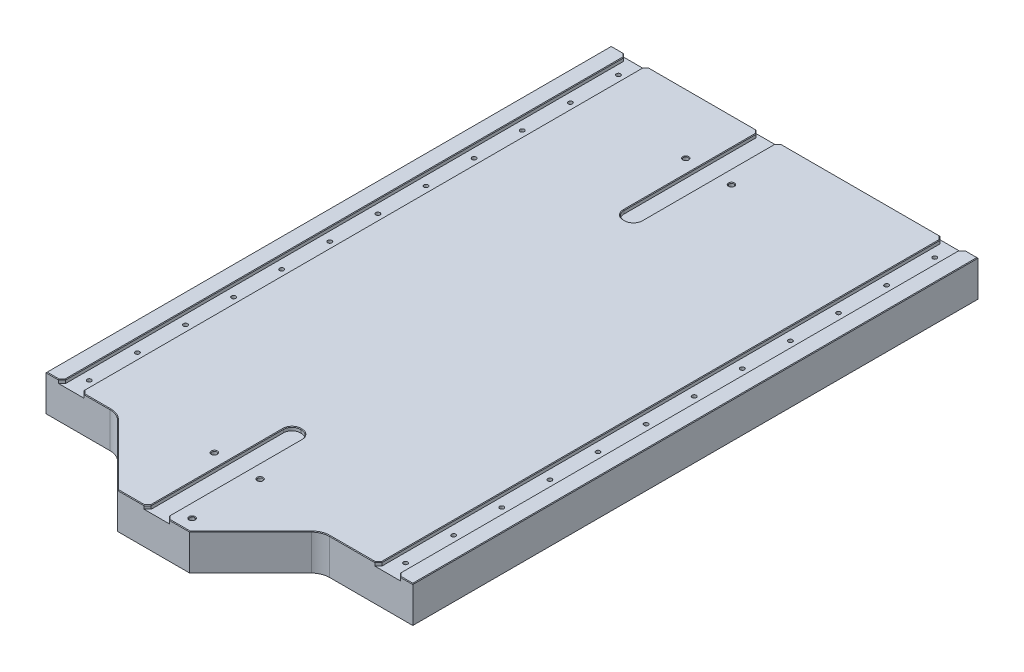
SolidWorks part; units mm, degrees
material "Acrylic (Medium-high impact)"
ref_plane "Front Plane" through (0, 0, 0) normal (0, 0, 1) x (1, 0, 0)
ref_plane "Top Plane" through (0, 0, 0) normal (0, 1, 0) x (1, 0, 0)
ref_plane "Right Plane" through (0, 0, 0) normal (1, 0, 0) x (0, 0, -1)
sketch "Sketch1" plane through (0, 0, 0) normal (0, 1, 0) x (1, 0, 0)
  line L0 (-93, -235) -> (-38, -290)
  line L1 (-152.5, -235) -> (-93, -235)
  line L2 (-152.5, -235) -> (-152.5, 235)
  line L3 (-152.5, 235) -> (152.5, 235)
  line L4 (152.5, -235) -> (152.5, 235)
  line L5 (-152.5, -235) -> (152.5, 235) construction
  line L6 (-152.5, 235) -> (152.5, -235) construction
  line L7 (-38, -290) -> (22, -290)
  line L8 (22, -290) -> (77, -235)
  line L10 (77, -235) -> (152.5, -235)
  point P0 (0, 0)
  point P10 (-38.351, -290.9295)
  point P11 (18.6696, -290.7914)
  point P12 (22.0738, -290)
  dimension "D1" = 305
  dimension "D2" = 470
  dimension "D3" = 45
  dimension "D4" = 45
  dimension "D5" = 55
  dimension "D6" = 22
  dimension "D7" = 60
extrude "Boss-Extrude1" add sketch "Sketch1" along normal blind 30
sketch "Sketch2" plane through (0, 0, 0) normal (0, 1, 0) x (1, 0, 0)
  line L0 (152.5, 235) -> (-152.5, 235) construction
  line L1 (-152.5, 235) -> (-152.5, -235) construction
  line L3 (-152.5, -235) -> (-93, -235) construction
  line L4 (0, 235) -> (0, -235) construction
  line L5 (152.5, 235) -> (-152.5, 235) construction
  line L6 (-152.5, -235) -> (-93, -235) construction
  circle A0 centre (-131.5, 220) radius 1.75
  circle A1 centre (131.5, 220) radius 1.75
  circle A4 centre (13.5, -223) radius 2
  circle A5 centre (-24.5, -223) radius 2
  circle A6 centre (-40.5, 185) radius 2
  circle A7 centre (-2.5, 185) radius 2
  circle A8 centre (131.5, -20) radius 1.75 [skipped]
  circle A9 centre (-131.5, -20) radius 1.75 [skipped]
  circle A10 centre (-131.5, 180) radius 1.75
  circle A11 centre (131.5, 180) radius 1.75
  circle A12 centre (-131.5, 140) radius 1.75
  circle A13 centre (131.5, 140) radius 1.75
  circle A14 centre (-131.5, 100) radius 1.75
  circle A15 centre (131.5, 100) radius 1.75
  circle A16 centre (-131.5, 60) radius 1.75
  circle A17 centre (131.5, 60) radius 1.75
  circle A18 centre (-131.5, 20) radius 1.75
  circle A19 centre (131.5, 20) radius 1.75
  circle A20 centre (-131.5, -20) radius 1.75
  circle A21 centre (131.5, -20) radius 1.75
  circle A22 centre (-131.5, -60) radius 1.75
  circle A23 centre (131.5, -60) radius 1.75
  circle A24 centre (-131.5, -100) radius 1.75
  circle A25 centre (131.5, -100) radius 1.75
  circle A26 centre (-131.5, -140) radius 1.75
  circle A27 centre (131.5, -140) radius 1.75
  circle A28 centre (-131.5, -180) radius 1.75
  circle A29 centre (131.5, -180) radius 1.75
  circle A30 centre (-131.5, -220) radius 1.75
  circle A31 centre (131.5, -220) radius 1.75
  circle A32 centre (13.5, -279.5) radius 2
  point P77 (4.7681, -277.9148)
  point P78 (0, 0)
  point P79 (13.5, -280.5297)
  dimension "D5" = 3.5
  dimension "D8" = 131.5
  dimension "D9" = 38
  dimension "D10" = 4
  dimension "D11" = 128
  dimension "D12" = 12
  dimension "D13" = 38
  dimension "D14" = 112
  dimension "D15" = 50
  dimension "D3" = 15
  dimension "D4" = 263
  dimension "D6" = 12
  dimension "D7" = 40
  dimension "D16" = 56.5
  dimension "D1" = 2
  dimension "D2" = 2
extrude "Cut-Extrude1" cut sketch "Sketch2" along normal through all
sketch "Sketch3" plane through (0, 30, 0) normal (0, 1, 0) x (1, 0, 0)
  line L0 (152.5, 235) -> (-152.5, 235) construction
  line L1 (-123.875, 235) -> (-139.125, 235)
  line L2 (-123.875, 235) -> (-123.875, -235)
  line L3 (-123.875, -235) -> (-139.125, -235)
  line L4 (-139.125, 235) -> (-139.125, -235)
  line L5 (-152.5, -235) -> (-93, -235) construction
  line L6 (0, 0) -> (0, 235) construction
  line L7 (-131.5, 235) -> (-131.5, 220) construction
  line L8 (123.875, -235) -> (139.125, -235)
  line L9 (123.875, 235) -> (123.875, -235)
  line L10 (123.875, 235) -> (139.125, 235)
  line L11 (131.5, 235) -> (131.5, 220) construction
  line L12 (139.125, 235) -> (139.125, -235)
  dimension "D1" = 15.25
extrude "Cut-Extrude2" cut sketch "Sketch3" against normal blind 3
sketch "Sketch4" plane through (0, 30, 0) normal (0, 1, 0) x (1, 0, 0)
  line L0 (13.5, -223) -> (-24.5, -223) construction
  line L1 (-5.5, -223) -> (-5.5, -230) construction
  line L2 (-38, -290) -> (22, -290) construction
  line L3 (2, -290) -> (-13, -290)
  line L4 (2, -290) -> (2, -170)
  line L5 (2, -170) -> (-13, -170)
  line L6 (-13, -290) -> (-13, -170)
  line L7 (2, -290) -> (-13, -170) construction
  line L8 (2, -170) -> (-13, -290) construction
  line L9 (-2.5, 185) -> (-40.5, 185) construction
  line L10 (-21.5, 185) -> (-21.5, 175) construction
  line L11 (123.875, 235) -> (-123.875, 235) construction
  line L12 (-14, 115) -> (-29, 115)
  line L13 (-14, 115) -> (-14, 235)
  line L14 (-14, 235) -> (-29, 235)
  line L15 (-29, 115) -> (-29, 235)
  line L16 (-14, 115) -> (-29, 235) construction
  line L17 (-14, 235) -> (-29, 115) construction
  dimension "D1" = 120
  dimension "D2" = 15
  dimension "D3" = 120
extrude "Cut-Extrude3" cut sketch "Sketch4" against normal blind 3
fillet "Fillet1" radius 7 4 edges at (-29, 28.5, -115) (-14, 28.5, -115) (-13, 28.5, 170) (2, 28.5, 170)
fillet "Fillet2" radius 15 2 edges at (77, 15, 235) (-93, 15, 235)
chamfer "Chamfer1" distance 3 angle 45 12 edges at (-139.125, 28.5, 235) (-123.875, 28.5, 235) (139.125, 28.5, 235) (123.875, 28.5, 235) (139.125, 28.5, -235) (123.875, 28.5, -235) (-123.875, 28.5, -235) (-139.125, 28.5, -235) (-14, 28.5, -235) (-29, 28.5, -235) (2, 28.5, 290) (-13, 28.5, 290)
chamfer "Chamfer2" distance 0.5 angle 45 47 edges at (140.625, 30, -233.5) (147.3125, 30, -235) (152.5, 30, 0) (147.3125, 30, 235) (140.625, 30, 233.5) (139.125, 30, 0) (-122.375, 30, -233.5) (-76.4375, 30, -235) (-30.5, 30, -233.5) (-29, 30, -177) (-26.9497, 30, -117.0503) (-21.5, 30, -115) (-16.0503, 30, -117.0503) (-14, 30, -177) (-12.5, 30, -233.5) (54.9375, 30, -235) (122.375, 30, -233.5) (123.875, 30, 0) (122.375, 30, 233.5) (102.0441, 30, 235) (77.473, 30, 236.1418) (47.3033, 30, 264.6967) (13.5, 30, 290) (3.5, 30, 288.5) (2, 30, 232) (-0.0503, 30, 172.0503) (-5.5, 30, 170) (-10.9497, 30, 172.0503) (-13, 30, 232) (-14.5, 30, 288.5) (-27, 30, 290) (-63.3033, 30, 264.6967) (-93.473, 30, 236.1418) (-110.0441, 30, 235) (-122.375, 30, 233.5) (-123.875, 30, 0) (13.5, 30, 281.5) (-2.5, 30, -183) (-40.5, 30, -183) (-24.5, 30, 225) (13.5, 30, 225) (-152.5, 30, 0) (-147.3125, 30, -235) (-140.625, 30, -233.5) (-139.125, 30, 0) (-140.625, 30, 233.5) (-147.3125, 30, 235)
